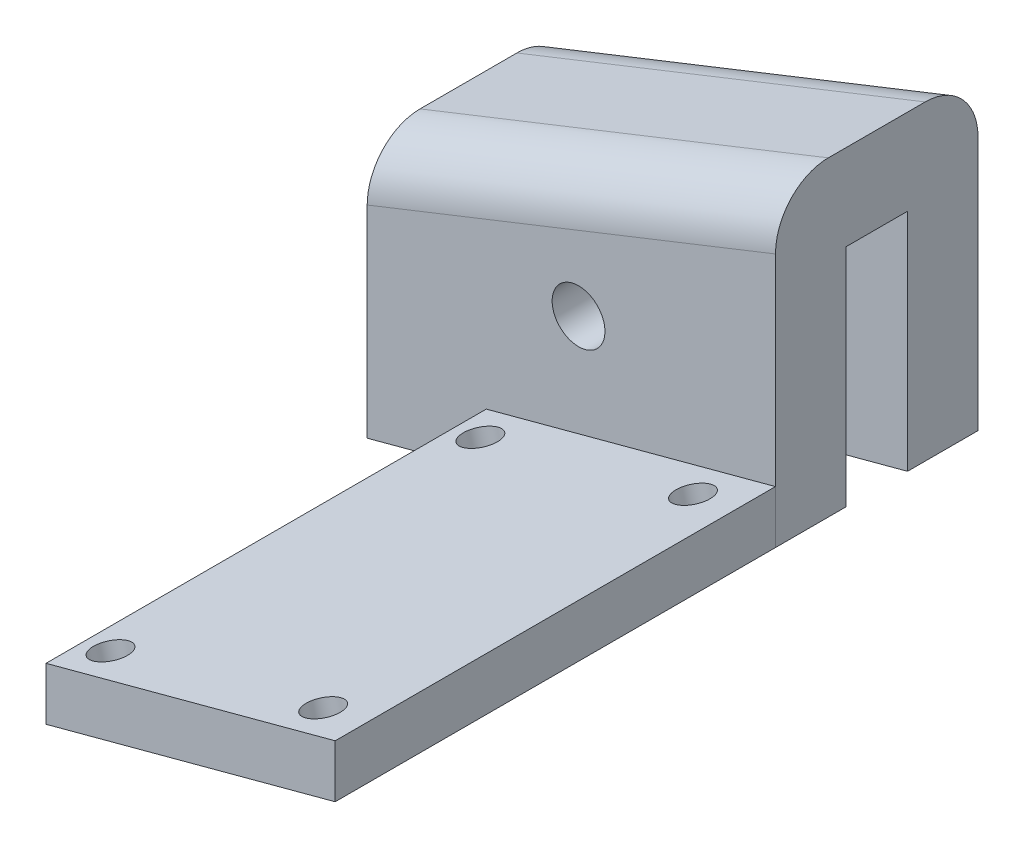
SolidWorks part; units mm, degrees
material "20% infill ABS"
ref_plane "Front" through (0, 0, 0) normal (0, 0, 1) x (1, 0, 0)
ref_plane "Top" through (0, 0, 0) normal (0, 1, 0) x (1, 0, 0)
ref_plane "Right" through (0, 0, 0) normal (1, 0, 0) x (0, 0, -1)
sketch "Sketch1" plane through (0, 0, 0) normal (0, 0, 1) x (1, 0, 0)
  line L0 (174.195, -57.9822) -> (197.3772, -51.7705) construction
  line L1 (174.195, -57.9822) -> (197.3772, -51.7705)
  line L2 (197.3772, -51.7705) -> (197.3772, -38.9795)
  line L3 (174.195, -57.9822) -> (174.195, -48.3445)
  line L4 (174.195, -48.3445) -> (174.195, -43.2884)
  line L5 (174.195, -43.2884) -> (197.3772, -34.1054)
  line L6 (197.3772, -34.1054) -> (197.3772, -38.9795)
  line L12 (83, 160.5) -> (80, 160.5)
  line L13 (80, 160.5) -> (80, 150.4)
  line L14 (80, 150.4) -> (83, 150.4)
  line L15 (83, 150.4) -> (83, 145.5)
  line L16 (288.0952, 47.05) -> (296.5952, 47.05)
  line L17 (296.5952, 47.05) -> (296.5952, 44.05)
  line L18 (296.5952, 44.05) -> (287.9228, 44.05)
  line L19 (155, -54.0482) -> (155, -59.5)
  line L20 (155, -59.5) -> (152, -59.5)
  line L21 (152, -59.5) -> (152, -64.5)
  line L22 (152, -64.5) -> (155, -64.5)
  line L23 (155, -64.5) -> (155, -69.5)
  parabola Q1 (155, -69.5) -> (306.0893, 45.5) focus (179.0197, 57.3821) apex (244.7409, -27.552)
  spline S3 degree 3 poles (1082.6492, 119.8917) (-59.8174, 135.2446) (25.7514, 146.2649) (93.6057, 145.4121) (101.0312, 145.2203) (109.7527, 144.8307) (121.1362, 144.0931) (134.9028, 142.7526) (150.6859, 140.4447) (165.7375, 137.4094) (184.8447, 132.3563) (206.9602, 124.0874) (226.8819, 113.0078) (241.6373, 102.2774) (252.1449, 93.237) (262.12, 83.1408) (270.0045, 73.7919) (276.0605, 65.7178) (280.4764, 59.358) (284.054, 53.7937) (313.7319, 4.9062) (336.8095, -69.6949) (-256.1865, 885.9345) knots -0.616279 -0.616279 -0.616279 -0.616279 0.021203 0.036364 0.066687 0.097009 0.127332 0.187977 0.248622 0.309268 0.369913 0.491203 0.612494 0.673139 0.733784 0.79443 0.855075 0.885398 0.91572 0.946043 0.961204 1.559696 1.559696 1.559696 1.559696 only from (83, 145.5) to (288.0952, 47.05)
  spline S4 degree 3 poles (-856.359, -1595.5436) (356.156, 248.4787) (333.343, 114.8639) (281.8203, 34.3276) (276.51, 26.644) (269.8135, 17.8999) (260.4469, 6.8608) (247.9167, -5.7866) (231.5398, -19.1667) (213.7827, -30.7858) (197.7951, -39.0188) (184.2662, -44.7377) (173.7465, -48.5916) (164.6591, -51.4408) (73.547, -76.5993) (-60.0444, -62.9954) (2062.3795, 545.7301) knots 0.49133 0.49133 0.49133 0.49133 0.497846 0.497983 0.498257 0.498531 0.498806 0.499354 0.499903 0.500451 0.500999 0.501274 0.501548 0.501822 0.501959 0.508255 0.508255 0.508255 0.508255 only from (287.9228, 44.05) to (155, -54.0482)
  spline S5 degree 3 poles (333.6076, -954.1208) (479.3551, 668.8846) (173.237, 29.6941) (-912.6161, 67.0926) knots -1.605787 -1.605787 -1.605787 -1.605787 2.973187 2.973187 2.973187 2.973187 only from (306.0893, 45.5) to (83, 160.5)
  spline S7 degree 3 poles (197.3772, -38.9795) (196.3743, -39.4518) (192.0638, -41.4415) (184.4282, -44.6692) (177.5888, -47.1837) (174.195, -48.3445) knots 0.500916 0.500916 0.500916 0.500916 0.500999 0.501274 0.501535 0.501535 0.501535 0.501535 construction
  dimension "D1" = 0
extrude "Boss-Extrude1" add sketch "Sketch1" along normal blind 4
sketch "Sketch2" plane through (0, 0, 4) normal (0, 0, 1) x (1, 0, 0)
  line L0 (197.3772, -51.7705) -> (197.3772, -48.7705)
  line L1 (197.3772, -51.7705) -> (197.3772, -34.1054) construction
  line L2 (197.3772, -48.7705) -> (180.9564, -53.1705)
  line L3 (180.9564, -53.1705) -> (180.9564, -56.1705)
  line L4 (174.195, -57.9822) -> (197.3772, -51.7705) construction
  line L5 (174.195, -57.9822) -> (197.3772, -51.7705) construction
  line L6 (180.9564, -56.1705) -> (197.3772, -51.7705)
  dimension "D1" = 3
  dimension "D2" = 17
extrude "Boss-Extrude2" add sketch "Sketch2" along normal up to surface (25 mm away) separate body
sketch "Sketch3" plane through (26.1644, -97.6469, 0) normal (0.2588, -0.9659, 0) x (0.9659, 0.2588, 0)
  circle A0 centre (162.7525, 6) radius 1 construction
  circle A1 centre (162.7525, 27) radius 1 construction
  circle A2 centre (175.2525, 6) radius 1 construction
  circle A3 centre (175.2525, 27) radius 1 construction
  circle A4 centre (162.7525, 6) radius 1
  circle A5 centre (162.7525, 27) radius 1
  circle A6 centre (175.2525, 6) radius 1
  circle A7 centre (175.2525, 27) radius 1
extrude "Cut-Extrude1" cut sketch "Sketch3" against normal blind 34
sketch "Sketch4" plane through (0, 0, 0) normal (0, 0, -1) x (-1, 0, 0)
  line L0 (-197.3772, -34.1054) -> (-174.195, -43.2884)
  line L1 (-174.195, -43.2884) -> (-174.195, -48.3445)
  line L2 (-174.195, -43.2884) -> (-174.195, -57.9822) construction
  line L3 (-197.3772, -34.1054) -> (-197.3772, -38.9795)
  line L4 (-197.3772, -51.7705) -> (-197.3772, -34.1054) construction
  line L17 (-80, 160.5) -> (-83, 160.5)
  line L18 (-80, 150.4) -> (-80, 160.5)
  line L19 (-83, 150.4) -> (-80, 150.4)
  line L20 (-83, 145.5) -> (-83, 150.4)
  line L21 (-296.5952, 47.05) -> (-288.0952, 47.05)
  line L22 (-296.5952, 44.05) -> (-296.5952, 47.05)
  line L23 (-287.9228, 44.05) -> (-296.5952, 44.05)
  line L24 (-155, -59.5) -> (-155, -54.0482)
  line L25 (-152, -59.5) -> (-155, -59.5)
  line L26 (-152, -64.5) -> (-152, -59.5)
  line L27 (-155, -64.5) -> (-152, -64.5)
  line L28 (-155, -69.5) -> (-155, -64.5)
  line L36 (-155, -59.5) -> (-155, -54.0482)
  line L37 (-152, -59.5) -> (-155, -59.5)
  line L38 (-152, -64.5) -> (-152, -59.5)
  line L39 (-155, -64.5) -> (-152, -64.5)
  line L40 (-155, -69.5) -> (-155, -64.5)
  parabola Q1 (-306.0893, 45.5) -> (-155, -69.5) focus (-179.0197, 57.3821) apex (-244.7409, -27.552)
  spline S3 degree 3 poles (256.1877, 885.9364) (-336.8096, -69.695) (-313.7319, 4.9062) (-284.054, 53.7937) (-280.4764, 59.358) (-276.0605, 65.7178) (-270.0045, 73.7919) (-262.12, 83.1408) (-252.1449, 93.237) (-241.6373, 102.2774) (-226.8819, 113.0078) (-206.9602, 124.0874) (-184.8447, 132.3563) (-165.7375, 137.4094) (-150.6859, 140.4447) (-134.9028, 142.7526) (-121.1362, 144.0931) (-109.7527, 144.8307) (-101.0312, 145.2203) (-93.6057, 145.4121) (-25.751, 146.2649) (59.8184, 135.2444) (-1082.6696, 119.8915) knots -0.583331 -0.583331 -0.583331 -0.583331 0.015161 0.030323 0.060645 0.090968 0.12129 0.181936 0.242581 0.303226 0.363871 0.485162 0.606452 0.667098 0.727743 0.788388 0.849033 0.879356 0.909679 0.940001 0.955163 1.592648 1.592648 1.592648 1.592648 only from (-288.0952, 47.05) to (-83, 145.5)
  spline S4 degree 3 poles (-2062.3893, 545.7329) (60.0448, -62.9953) (-73.5469, -76.5993) (-164.6591, -51.4408) (-173.7465, -48.5916) (-184.2662, -44.7377) (-197.7951, -39.0188) (-213.7827, -30.7858) (-231.5398, -19.1667) (-247.9167, -5.7866) (-260.4469, 6.8608) (-269.8135, 17.8999) (-276.51, 26.644) (-281.8203, 34.3276) (-333.3431, 114.8641) (-356.1561, 248.4794) (856.3685, -1595.558) knots 0.49151 0.49151 0.49151 0.49151 0.497806 0.497943 0.498217 0.498491 0.498765 0.499314 0.499862 0.500411 0.500959 0.501233 0.501508 0.501782 0.501919 0.508435 0.508435 0.508435 0.508435 only from (-155, -54.0482) to (-287.9228, 44.05)
  spline S5 degree 3 poles (912.6271, 67.093) (-173.2309, 29.6899) (-479.3533, 668.8854) (-333.6092, -954.1027) knots -1.973203 -1.973203 -1.973203 -1.973203 2.60577 2.60577 2.60577 2.60577 only from (-83, 160.5) to (-306.0893, 45.5)
  spline S7 degree 3 poles (-174.195, -48.3445) (-177.5888, -47.1837) (-184.4282, -44.6692) (-192.0638, -41.4415) (-196.3743, -39.4518) (-197.3772, -38.9795) knots 0.49823 0.49823 0.49823 0.49823 0.498491 0.498765 0.498849 0.498849 0.498849 0.498849
  line M20 (-174.195, -43.2884) -> (-197.3772, -34.1054)
  line M21 (-197.3772, -34.1054) -> (-197.3772, -51.7705)
  line M23 (-174.195, -57.9822) -> (-174.195, -43.2884)
  dimension "D1" = 0
extrude "Boss-Extrude3" add sketch "Sketch4" along normal blind 3.5 contours S7 M23 M20 M21 region at (185.7229, -41.3302, 0)
sketch "Sketch5" plane through (0, 0, -3.5) normal (0, 0, -1) x (-1, 0, 0)
  line L4 (-174.195, -43.2884) -> (-197.3772, -34.1054)
  line L5 (-174.195, -57.9822) -> (-174.195, -43.2884)
  line L6 (-197.3772, -51.7705) -> (-174.195, -57.9822)
  line L7 (-197.3772, -34.1054) -> (-197.3772, -51.7705)
  line L8 (-174.195, -43.2884) -> (-197.3772, -34.1054)
  line L9 (-174.195, -57.9822) -> (-174.195, -43.2884)
  line L10 (-197.3772, -51.7705) -> (-174.195, -57.9822)
  line L11 (-197.3772, -34.1054) -> (-197.3772, -51.7705)
  dimension "D1" = 0
extrude "Boss-Extrude4" add sketch "Sketch5" along normal blind 4
sketch "Sketch6" plane through (0, 0, -7.5) normal (0, 0, -1) x (-1, 0, 0)
  circle A0 centre (-186.195, -45.9822) radius 1.5
  dimension "D3" = 3
  dimension "D1" = 12
  dimension "D2" = 12
extrude "Cut-Extrude2" cut sketch "Sketch6" against normal blind 34
fillet "Fillet1" radius 3 2 edges at (185.7861, -38.6969, -7.5) (185.7861, -38.6969, 4)
